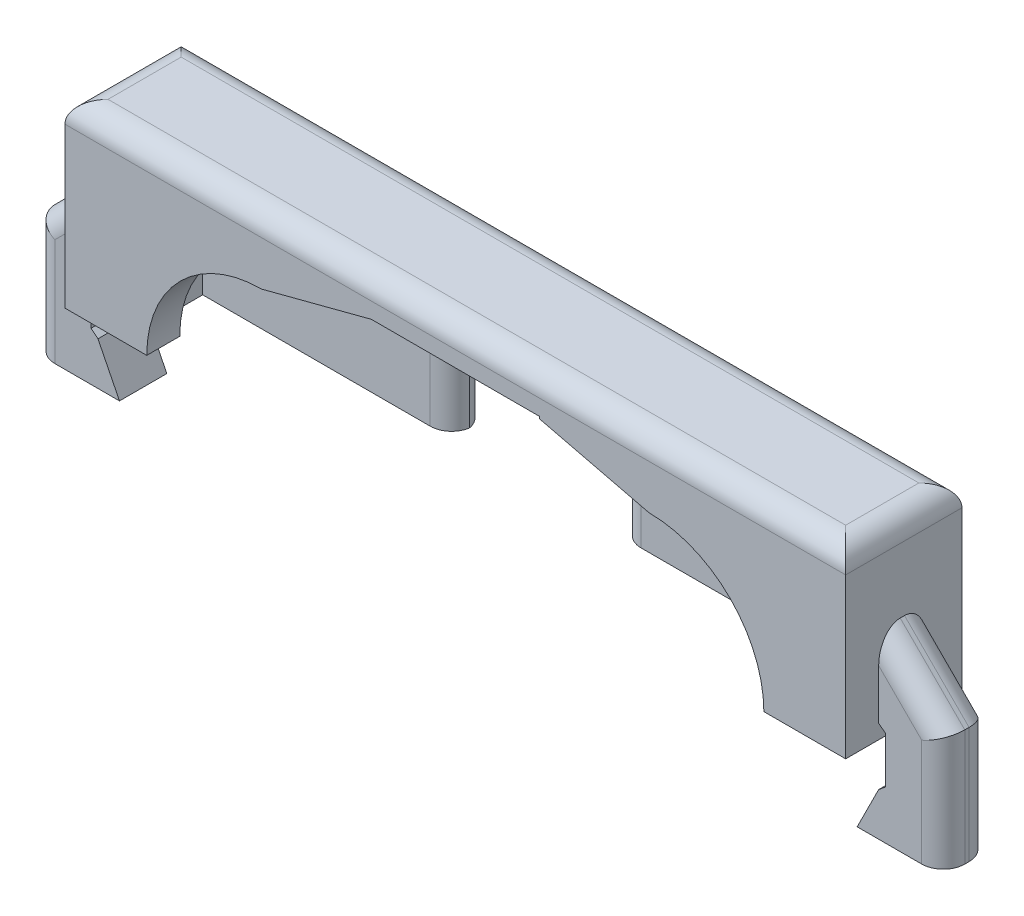
SolidWorks part; units mm, degrees
ref_plane "Front Plane" through (0, 0, 0) normal (0, 0, 1) x (1, 0, 0)
ref_plane "Top Plane" through (0, 0, 0) normal (0, 1, 0) x (1, 0, 0)
ref_plane "Right Plane" through (0, 0, 0) normal (1, 0, 0) x (0, 0, -1)
sketch "Sketch1" plane through (0, 0, 0) normal (0, 1, 0) x (1, 0, 0)
  line L1 (-27.2, -4.05) -> (27.2, -4.05)
  line L2 (-27.2, -4.05) -> (-27.2, 4.05)
  line L3 (-27.2, 4.05) -> (27.2, 4.05)
  line L4 (27.2, -4.05) -> (27.2, 4.05)
  line L5 (-27.2, -4.05) -> (27.2, 4.05) construction
  line L6 (-27.2, 4.05) -> (27.2, -4.05) construction
  line L7 (-23.2, -1.75) -> (23.2, -1.75)
  line L8 (-23.2, -1.75) -> (-23.2, 1.55)
  line L9 (-23.2, 1.55) -> (23.2, 1.55)
  line L10 (23.2, -1.75) -> (23.2, 1.55)
  point P0 (0, 0)
  dimension "D1" = 54.4
  dimension "D2" = 8.1
  dimension "D3" = 2.5
  dimension "D4" = 4
  dimension "D5" = 4
  dimension "D6" = 2.3
extrude "Boss-Extrude1" add sketch "Sketch1" along normal blind 10
sketch "Sketch2" plane through (0, 0, -1.55) normal (0, 0, 1) x (1, 0, 0)
  line L0 (-27.2, 10) -> (27.2, 10) construction
  line L1 (-5.85, 10) -> (5.85, 10)
  line L2 (-5.85, 10) -> (-5.85, -10)
  line L3 (-5.85, -10) -> (5.85, -10)
  line L4 (5.85, 10) -> (5.85, -10)
  line L5 (-27.2, 10) -> (-27.2, 0) construction
  dimension "D1" = 11.7
  dimension "D2" = 20
  dimension "D3" = 0
  dimension "D4" = 21.35
  dimension "D5" = 5.85
extrude "Cut-Extrude1" cut sketch "Sketch2" against normal blind 10
sketch "Sketch3" plane through (0, 0, 1.75) normal (0, 0, -1) x (-1, 0, 0)
  line L0 (-27.2, 0) -> (-5.85, 0) construction
  circle A0 centre (-13.5, 0) radius 8
  circle A1 centre (13.5, 0) radius 8
  dimension "D1" = 27
  dimension "D2" = 13.5
extrude "Cut-Extrude2" cut sketch "Sketch3" against normal blind 10
sketch "Sketch4" plane through (0, 10, 0) normal (0, 1, 0) x (1, 0, 0)
  line L1 (-27.2, -4.05) -> (27.2, -4.05)
  line L2 (-27.2, -4.05) -> (-27.2, 4.05)
  line L3 (-27.2, 4.05) -> (27.2, 4.05)
  line L4 (27.2, -4.05) -> (27.2, 4.05)
extrude "Boss-Extrude2" add sketch "Sketch4" along normal blind 2.6
sketch "Sketch5" plane through (0, 0, -1.55) normal (0, 0, 1) x (1, 0, 0)
  line L0 (27.2, -6) -> (25.7, -6)
  line L1 (29.7, -0.95) -> (27.2, -3)
  line L2 (-27.2, 6.6) -> (-27.2, 1.002)
  line L3 (-27.2, -6) -> (-29.7, -6)
  line L5 (-27.2, 12.6) -> (-27.2, 0) construction
  line L6 (-27.2, 0) -> (-21.5, 0) construction
  line L7 (-29.7, 4.1) -> (-31.7, 2.1)
  line L8 (-27.2, 6.6) -> (-29.7, 4.1)
  line L9 (27.2, -3) -> (25.7, -6)
  line L10 (-29.7, -6) -> (-31.7, -6)
  line L11 (-31.7, -6) -> (-31.7, 2.1)
  line L12 (-27.2, 1.002) -> (-29.7, -0.95)
  line L13 (27.2, -6) -> (29.7, -6)
  line L14 (29.7, -6) -> (31.7, -6)
  line L15 (31.7, -6) -> (31.7, 2.1)
  line L16 (27.2, 6.6) -> (27.2, 1.002)
  line L17 (-27.2, -6) -> (-25.7, -6)
  line L18 (-27.2, -3) -> (-25.7, -6)
  line L19 (-29.7, -0.95) -> (-27.2, -3)
  line L20 (29.7, 4.1) -> (31.7, 2.1)
  line L21 (27.2, 6.6) -> (29.7, 4.1)
  line L22 (27.2, 1.002) -> (29.7, -0.95)
  dimension "D2" = 0
  dimension "D4" = 6
extrude "Boss-Extrude3" add sketch "Sketch5" along normal blind 3.3
extrude "Cut-Extrude3" cut sketch "Sketch2<2>" along normal blind 20
sketch "Sketch2<2>" plane through (0, 0, -1.55) normal (0, 0, 1) x (1, 0, 0) same geometry as "Sketch2"
sketch "Sketch6" plane through (0, 0, 4.05) normal (0, 0, 1) x (1, 0, 0)
  line L0 (-13.5, 8) -> (-5.85, 10)
  line L1 (-5.85, 10) -> (5.25, 10)
  line L2 (5.85, 10) -> (-5.85, 10) construction
  line L3 (5.25, 10) -> (13.5, 8)
  line L4 (-13.5, -8) -> (13.5, -8)
  arc A0 (-13.5, 8) -> (-13.5, -8) centre (-13.5, 0) ccw
  arc A1 (13.5, -8) -> (13.5, 8) centre (13.5, 0) ccw
extrude "Cut-Extrude4" cut sketch "Sketch6" against normal blind 5
sketch "Sketch7" plane through (0, 0, 1.75) normal (0, 0, 1) x (1, 0, 0)
  line L1 (-30.4584, 0.9685) -> (-27.6804, 0.9685)
  line L2 (-30.4584, 0.9685) -> (-30.4584, -3.9922)
  line L3 (-30.4584, -3.9922) -> (-27.6804, -3.9922)
  line L4 (-27.6804, 0.9685) -> (-27.6804, -3.9922)
  line L5 (27.6804, 0.9685) -> (27.6804, -3.9922)
  line L6 (30.4584, -3.9922) -> (27.6804, -3.9922)
  line L7 (30.4584, 0.9685) -> (30.4584, -3.9922)
  line L8 (30.4584, 0.9685) -> (27.6804, 0.9685)
extrude "Boss-Extrude4" add sketch "Sketch7" against normal blind 3.3
fillet "Fillet1" radius 1.5 4 edges at (27.2, 12.6, 0) (-27.2, 12.6, 0) (0, 12.6, -4.05) (0, 12.6, 4.05)
fillet "Fillet2" radius 1.5 2 edges at (5.85, 5, -1.55)
fillet "Fillet3" radius 1.5 2 edges at (-5.85, 5, -1.55)
fillet "Fillet4" radius 1.5 8 edges at (31.7, -1.95, -1.55) (29.45, 4.35, -1.55) (31.7, -1.95, 1.75) (29.45, 4.35, 1.75) (-29.45, 4.35, -1.55) (-29.45, 4.35, 1.75) (-31.7, -1.95, -1.55) (-31.7, -1.95, 1.75)
